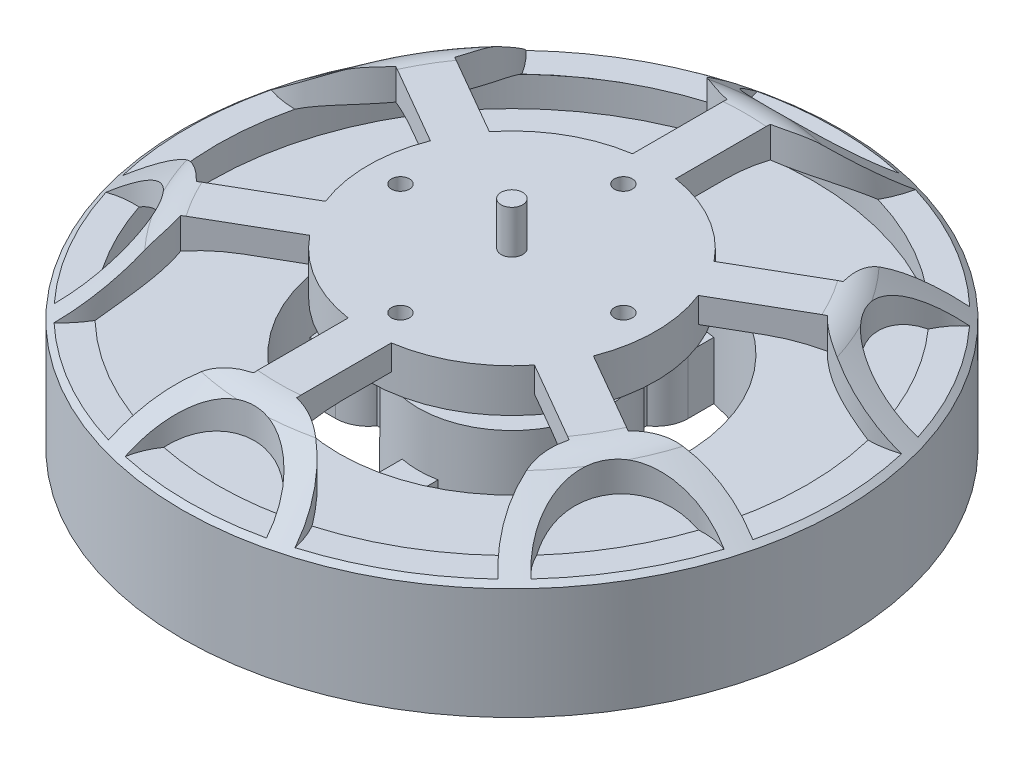
SolidWorks part; units mm, degrees
ref_plane "Front Plane" through (0, 0, 0) normal (0, 0, 1) x (1, 0, 0)
ref_plane "Top Plane" through (0, 0, 0) normal (0, 1, 0) x (1, 0, 0)
ref_plane "Right Plane" through (0, 0, 0) normal (1, 0, 0) x (0, 0, -1)
ref_plane "Plane1" through (0, 0, 0) normal (-0.7071, 0, 0.7071) x (0.7071, 0, 0.7071)
ref_axis "Axis1" through (0, 40.089, 0) along (0, -1, 0)
sketch "Sketch1" plane through (0, 0, 0) normal (0, 0, 1) x (1, 0, 0)
  line L0 (0, 0) -> (9.65, 0)
  line L1 (9.65, 0) -> (9.65, 3.93)
  line L2 (9.65, 3.93) -> (27.5, 3.93)
  line L3 (27.5, 3.93) -> (45.83, 8.08)
  line L4 (45.83, 8.08) -> (45.83, 23.58)
  line L5 (45.83, 23.58) -> (36.1322, 30.9557)
  line L6 (32.5, 32.18) -> (1.5, 32.18)
  line L7 (1.5, 32.18) -> (1.5, 38.18)
  line L8 (1.5, 38.18) -> (0, 38.18)
  line L9 (0, 38.18) -> (0, 0) construction
  line L10 (0, 0) -> (0, 38.18)
  arc A0 (36.1322, 30.9557) -> (32.5, 32.18) centre (32.5, 26.18) ccw
  dimension "D10" = 6
  dimension "D1" = 3
  dimension "D2" = 6
  dimension "D3" = 28.25
  dimension "D4" = 3.93
  dimension "D5" = 19.3
  dimension "D6" = 4.15
  dimension "D7" = 91.66
  dimension "D8" = 55
  dimension "D9" = 65
  dimension "D11" = 15.5
revolve "Revolve1" add sketch "Sketch1" angle 360 about L9
sketch "Sketch2" plane through (0, 3.93, 0) normal (0, -1, 0) x (1, 0, 0)
  line L0 (0, 0) -> (0, 27.5) construction
  line L1 (2.5, 12.7574) -> (2.5, 16.2583)
  line L2 (4.5, 20) -> (4.5, 23.5744)
  line L3 (0, 0) -> (16.9706, 16.9706) construction
  line L4 (20, 4.5) -> (23.5744, 4.5)
  line L5 (12.7574, 2.5) -> (16.2583, 2.5)
  line L6 (20, -4.5) -> (23.5744, -4.5)
  line L7 (4.5, -20) -> (4.5, -23.5744)
  line L8 (2.5, -12.7574) -> (2.5, -16.2583)
  line L9 (12.7574, -2.5) -> (16.2583, -2.5)
  line L10 (-4.5, -20) -> (-4.5, -23.5744)
  line L11 (-20, -4.5) -> (-23.5744, -4.5)
  line L12 (-12.7574, -2.5) -> (-16.2583, -2.5)
  line L13 (-2.5, -12.7574) -> (-2.5, -16.2583)
  line L14 (-20, 4.5) -> (-23.5744, 4.5)
  line L15 (-4.5, 20) -> (-4.5, 23.5744)
  line L16 (-2.5, 12.7574) -> (-2.5, 16.2583)
  line L17 (-12.7574, 2.5) -> (-16.2583, 2.5)
  arc A0 (4.5, 23.5744) -> (23.5744, 4.5) centre (0, 0) cw
  arc A1 (4.5, 20) -> (2.5, 16.2583) centre (0, 20) cw
  arc A2 (2.5, 12.7574) -> (12.7574, 2.5) centre (0, 0) cw
  circle A3 centre (0, 0) radius 27.5 construction
  arc A4 (20, 4.5) -> (16.2583, 2.5) centre (20, 0) ccw
  arc A5 (20, -4.5) -> (16.2583, -2.5) centre (20, 0) cw
  arc A6 (23.5744, -4.5) -> (4.5, -23.5744) centre (0, 0) cw
  arc A7 (4.5, -20) -> (2.5, -16.2583) centre (0, -20) ccw
  arc A8 (12.7574, -2.5) -> (2.5, -12.7574) centre (0, 0) cw
  arc A9 (-4.5, -20) -> (-2.5, -16.2583) centre (0, -20) cw
  arc A10 (-4.5, -23.5744) -> (-23.5744, -4.5) centre (0, 0) cw
  arc A11 (-20, -4.5) -> (-16.2583, -2.5) centre (-20, 0) ccw
  arc A12 (-2.5, -12.7574) -> (-12.7574, -2.5) centre (0, 0) cw
  arc A13 (-20, 4.5) -> (-16.2583, 2.5) centre (-20, 0) cw
  arc A14 (-23.5744, 4.5) -> (-4.5, 23.5744) centre (0, 0) cw
  arc A15 (-4.5, 20) -> (-2.5, 16.2583) centre (0, 20) ccw
  arc A16 (-12.7574, 2.5) -> (-2.5, 12.7574) centre (0, 0) cw
  point P4 (0, 20)
  point P51 (0, 0)
  dimension "D2" = 13
  dimension "D5" = 24
  dimension "D1" = 20
  dimension "D3" = 5
  dimension "D4" = 9
  dimension "D6" = 45
  dimension "D7" = 4
hole_wizard "M4x0.7 Tapped Hole1" positions "3DSketch1" profile "Sketch4" tap size "M4x0.7" standard "ANSI Metric"
sketch3d "3DSketch1"
  point P0 (-20, 3.93, 0)
  point P3 (0, 3.93, 20)
  point P6 (20, 3.93, 0)
  point P9 (0, 3.93, -20)
sketch "Sketch4" plane through (-20, 3.93, 0) normal (1, 0, 0) x (0, 0, -1)
  line L0 (0, 0) -> (0, 8.9914)
  line L1 (0, 8.9914) -> (1.65, 8)
  line L2 (1.65, 8) -> (1.65, 0)
  line L5 (1.65, 0) -> (0, 0)
  line L10 (0, 8.9914) -> (-1.65, 8) construction
  line L11 (0, -6.35) -> (0, 107.95) construction
  dimension "Tap Drill Dia." = 3.3
  dimension "Tap Drill Depth" = 8
  dimension "Drill Angle" = 118
cosmetic thread "Hole Thread1" parameters "D1"=7.874, "D2"=4
cosmetic thread "Hole Thread2" parameters "D1"=7.874, "D2"=4
cosmetic thread "Hole Thread3" parameters "D1"=7.874, "D2"=4
cosmetic thread "Hole Thread4" parameters "D1"=7.874, "D2"=4
extrude "Cut-Extrude1" cut sketch "Sketch2" against normal blind 8
sketch "Sketch5" plane through (0, 0, 0) normal (0, 0, 1) x (1, 0, 0)
  line L0 (24, 19.43) -> (41.83, 19.43)
  line L1 (-27.5, 3.93) -> (27.5, 3.93) construction
  line L2 (41.83, 19.43) -> (41.83, 23.58)
  line L3 (45.83, 8.08) -> (45.83, 23.58) construction
  line L4 (10, 19.43) -> (13, 19.43)
  line L5 (13, 19.43) -> (13, 11.93)
  line L6 (13, 11.93) -> (24, 11.93)
  line L7 (24, 11.93) -> (24, 19.43)
  line L8 (0, 40.089) -> (0, -1.909) construction
  line L9 (4.5, 11.93) -> (23.5744, 11.93) construction
  line L10 (45.83, 23.58) -> (-45.83, 23.58) construction
  line L11 (20, 28.68) -> (26.6996, 28.68)
  line L12 (32.5, 32.18) -> (-32.5, 32.18) construction
  line L13 (41.83, 23.58) -> (45.83, 20.5378) construction
  line L14 (45.83, 23.58) -> (36.1322, 30.9557) construction
  line L15 (20, 28.68) -> (20, 26.18)
  line L16 (20, 26.18) -> (10, 26.18)
  line L17 (10, 26.18) -> (10, 19.43)
  arc A0 (26.6996, 28.68) -> (41.83, 23.58) centre (26.6996, 3.6861) cw
  dimension "D1" = 15.5
  dimension "D2" = 4
  dimension "D3" = 13
  dimension "D4" = 24
  dimension "D5" = 3.5
  dimension "D6" = 20
  dimension "D7" = 6
  dimension "D8" = 10
revolve "Cut-Revolve3" cut sketch "Sketch5" angle 360 about axis through (0, 40.089, 0) along (0, -1, 0)
sketch "Sketch6" plane through (0, 0, 0) normal (0, 1, 0) x (1, 0, 0)
  line L0 (-3, 19.7737) -> (-3, 32.9241)
  line L1 (3, 19.7737) -> (3, 32.9241)
  line L2 (-3, 19.7737) -> (3, 19.7737) construction
  line L3 (0, 45.83) -> (0, 35.83) construction
  line L4 (15.6245, 12.4849) -> (27.0131, 19.0601)
  line L5 (18.6245, 7.2888) -> (30.0131, 13.864)
  line L6 (15.6245, 12.4849) -> (18.6245, 7.2888) construction
  line L7 (39.6899, 22.915) -> (31.0297, 17.915) construction
  line L8 (18.6245, -7.2888) -> (30.0131, -13.864)
  line L9 (15.6245, -12.4849) -> (27.0131, -19.0601)
  line L10 (18.6245, -7.2888) -> (15.6245, -12.4849) construction
  line L11 (39.6899, -22.915) -> (31.0297, -17.915) construction
  line L12 (3, -19.7737) -> (3, -32.9241)
  line L13 (-3, -19.7737) -> (-3, -32.9241)
  line L14 (3, -19.7737) -> (-3, -19.7737) construction
  line L15 (0, -45.83) -> (0, -35.83) construction
  line L16 (-15.6245, -12.4849) -> (-27.0131, -19.0601)
  line L17 (-18.6245, -7.2888) -> (-30.0131, -13.864)
  line L18 (-15.6245, -12.4849) -> (-18.6245, -7.2888) construction
  line L19 (-39.6899, -22.915) -> (-31.0297, -17.915) construction
  line L20 (-18.6245, 7.2888) -> (-30.0131, 13.864)
  line L21 (-15.6245, 12.4849) -> (-27.0131, 19.0601)
  line L22 (-18.6245, 7.2888) -> (-15.6245, 12.4849) construction
  line L23 (-39.6899, 22.915) -> (-31.0297, 17.915) construction
  line L24 (0, 15.5) -> (15.5, 0) construction
  line L25 (15.5, 0) -> (0, -15.5) construction
  line L26 (0, -15.5) -> (-15.5, 0) construction
  line L27 (-15.5, 0) -> (0, 15.5) construction
  arc A1 (-9.9403, 44.739) -> (9.9403, 44.739) centre (0, 45.83) ccw
  circle A2 centre (0, 0) radius 45.83 construction
  arc A3 (-13.1108, 43.9146) -> (-3, 32.9241) centre (0, 45.83) ccw
  arc A4 (13.1108, 43.9146) -> (3, 32.9241) centre (0, 45.83) cw
  arc A5 (-13.1108, 43.9146) -> (-9.9403, 44.739) centre (0, 0) cw
  arc A6 (9.9403, 44.739) -> (13.1108, 43.9146) centre (0, 0) cw
  arc A7 (33.775, 30.9781) -> (43.7153, 13.7609) centre (39.6899, 22.915) ccw
  arc A8 (31.4758, 33.3116) -> (27.0131, 19.0601) centre (39.6899, 22.915) ccw
  arc A9 (44.5866, 10.603) -> (30.0131, 13.864) centre (39.6899, 22.915) cw
  arc A10 (31.4758, 33.3116) -> (33.775, 30.9781) centre (0, 0) cw
  arc A11 (43.7153, 13.7609) -> (44.5866, 10.603) centre (0, 0) cw
  arc A12 (43.7153, -13.7609) -> (33.775, -30.9781) centre (39.6899, -22.915) ccw
  arc A13 (44.5866, -10.603) -> (30.0131, -13.864) centre (39.6899, -22.915) ccw
  arc A14 (31.4758, -33.3116) -> (27.0131, -19.0601) centre (39.6899, -22.915) cw
  arc A15 (44.5866, -10.603) -> (43.7153, -13.7609) centre (0, 0) cw
  arc A16 (33.775, -30.9781) -> (31.4758, -33.3116) centre (0, 0) cw
  arc A17 (9.9403, -44.739) -> (-9.9403, -44.739) centre (0, -45.83) ccw
  arc A18 (13.1108, -43.9146) -> (3, -32.9241) centre (0, -45.83) ccw
  arc A19 (-13.1108, -43.9146) -> (-3, -32.9241) centre (0, -45.83) cw
  arc A20 (13.1108, -43.9146) -> (9.9403, -44.739) centre (0, 0) cw
  arc A21 (-9.9403, -44.739) -> (-13.1108, -43.9146) centre (0, 0) cw
  arc A22 (-33.775, -30.9781) -> (-43.7153, -13.7609) centre (-39.6899, -22.915) ccw
  arc A23 (-31.4758, -33.3116) -> (-27.0131, -19.0601) centre (-39.6899, -22.915) ccw
  arc A24 (-44.5866, -10.603) -> (-30.0131, -13.864) centre (-39.6899, -22.915) cw
  arc A25 (-31.4758, -33.3116) -> (-33.775, -30.9781) centre (0, 0) cw
  arc A26 (-43.7153, -13.7609) -> (-44.5866, -10.603) centre (0, 0) cw
  arc A27 (-43.7153, 13.7609) -> (-33.775, 30.9781) centre (-39.6899, 22.915) ccw
  arc A28 (-44.5866, 10.603) -> (-30.0131, 13.864) centre (-39.6899, 22.915) ccw
  arc A29 (-31.4758, 33.3116) -> (-27.0131, 19.0601) centre (-39.6899, 22.915) cw
  arc A30 (-44.5866, 10.603) -> (-43.7153, 13.7609) centre (0, 0) cw
  arc A31 (-33.775, 30.9781) -> (-31.4758, 33.3116) centre (0, 0) cw
  arc A32 (3, 19.7737) -> (15.6245, 12.4849) centre (0, 0) cw
  arc A33 (18.6245, 7.2888) -> (18.6245, -7.2888) centre (0, 0) cw
  arc A34 (15.6245, -12.4849) -> (3, -19.7737) centre (0, 0) cw
  arc A35 (-3, -19.7737) -> (-15.6245, -12.4849) centre (0, 0) cw
  arc A36 (-18.6245, -7.2888) -> (-18.6245, 7.2888) centre (0, 0) cw
  arc A37 (-3, 19.7737) -> (-15.6245, 12.4849) centre (0, 0) ccw
  point P0 (0, 19.7737)
  point P17 (0, 15.5)
  point P28 (15.5, 0)
  point P38 (0, -15.5)
  point P68 (0, 0)
  point P69 (-15.5, 0)
  dimension "D1" = 6
  dimension "D3" = 3.25
  dimension "D5" = 20
  dimension "D2" = 6
  dimension "D4" = 10
  dimension "D6" = 15.5
extrude "Cut-Extrude3" cut sketch "Sketch6" against normal blind 8 from surface flip side to cut starting at face at (0, 32.18, 1.5)
hole_wizard "M3x0.5 Tapped Hole1" positions "Sketch8" profile "Sketch10" tap size "M3x0.5" standard "ANSI Metric" end condition up to next
sketch "Sketch8" plane through (0, 32.18, 0) normal (0, 1, 0) x (1, 0, 0)
  point P0 (0, 15.5)
  point P3 (15.5, 0)
  point P6 (0, -15.5)
  point P9 (-15.5, 0)
sketch "Sketch10" plane through (0, 32.18, -15.5) normal (1, 0, 0) x (0, 0, 1)
  line L0 (0, 0) -> (0, 6)
  line L1 (0, 6) -> (1.25, 6)
  line L2 (1.25, 6) -> (1.25, 0)
  line L5 (1.25, 0) -> (0, 0)
  line L11 (0, -6.35) -> (0, 107.95) construction
  dimension "Thru Tap Drill Dia." = 2.5
  dimension "Thru Tap Drill Depth" = 6
cosmetic thread "Hole Thread5" parameters "D2"=3
cosmetic thread "Hole Thread6" parameters "D2"=3
cosmetic thread "Hole Thread7" parameters "D2"=3
cosmetic thread "Hole Thread8" parameters "D2"=3
sketch "Sketch11" plane through (0, 0, 0) normal (0, 1, 0) x (1, 0, 0)
  line L0 (-26.0427, 21.4465) -> (-21.4465, 26.0427) construction
  line L1 (-27.9873, 23.3911) -> (-23.3911, 27.9873)
  line L2 (-24.0982, 19.502) -> (-19.502, 24.0982)
  line L3 (-23.7446, 23.7446) -> (0, 0) construction
  line L4 (-20, 0) -> (0, 20) construction
  line L5 (-27.9873, 19.502) -> (-19.502, 27.9873) construction
  line L6 (-25.6892, 25.6892) -> (-32.4067, 32.4067) construction
  arc A0 (-27.9873, 23.3911) -> (-24.0982, 19.502) centre (-26.0427, 21.4465) ccw
  arc A1 (-19.502, 24.0982) -> (-23.3911, 27.9873) centre (-21.4465, 26.0427) ccw
  arc A2 (3, 19.7737) -> (-3, 19.7737) centre (0, 0) ccw construction
  circle A3 centre (0, 0) radius 45.83 construction
  point P2 (-23.7446, 23.7446)
  dimension "D1" = 12
  dimension "D2" = 5.5
  dimension "D3" = 9.5
extrude "Boss-Extrude1" add sketch "Sketch11" against normal blind 19.05 from offset 12.7
equation "\"INTERIOR_STATOR_BORE_OD\"= 48MM"
equation "\"INTERIOR_STATOR_BORE_ID\"= 26mm"
equation "\"D5@Sketch2\"=\"INTERIOR_STATOR_BORE_OD\"/2"
equation "\"D2@Sketch2\"=\"INTERIOR_STATOR_BORE_ID\"/2"
equation "\"D3@Sketch5\"=\"INTERIOR_STATOR_BORE_ID\"/2"
equation "\"D4@Sketch5\"=\"INTERIOR_STATOR_BORE_OD\"/2"
